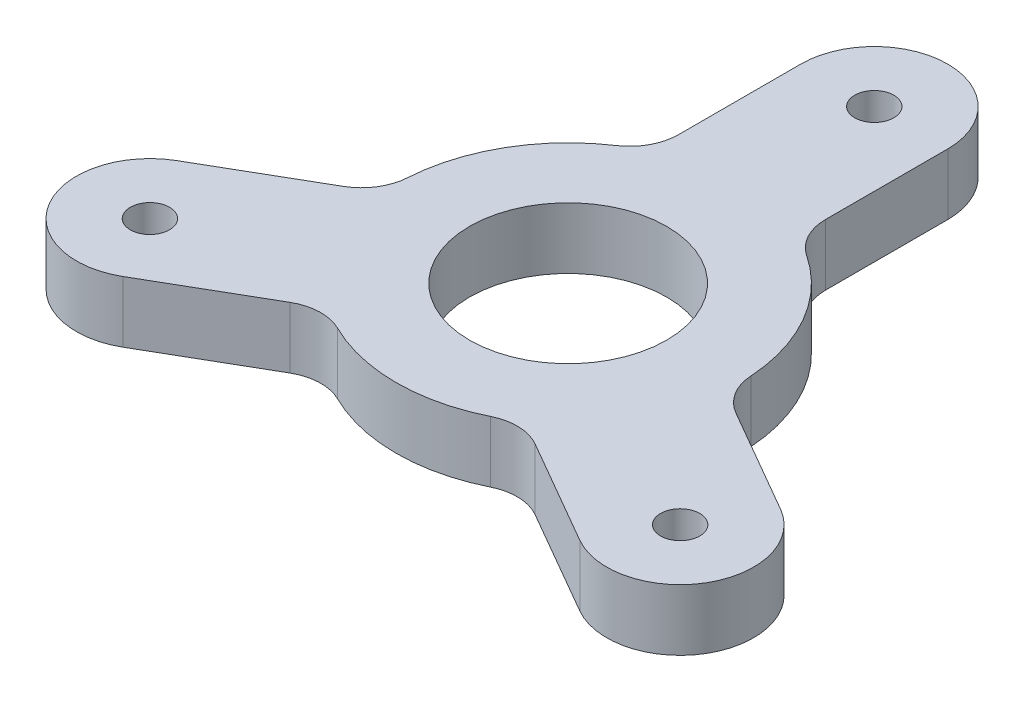
SolidWorks part; units mm, degrees
ref_plane "Front Plane" through (0, 0, 0) normal (0, 0, 1) x (1, 0, 0)
ref_plane "Top Plane" through (0, 0, 0) normal (0, 1, 0) x (1, 0, 0)
ref_plane "Right Plane" through (0, 0, 0) normal (1, 0, 0) x (0, 0, -1)
sketch "Sketch1" plane through (0, 0, 0) normal (0, 1, 0) x (1, 0, 0)
  line L0 (0, 0) -> (0, 9.0907) construction
  line L1 (0, 0) -> (7.1459, -4.1257) construction
  line L2 (0, 0) -> (-8.3205, -4.8039) construction
  line L3 (24.6506, -7.3038) -> (16.0135, -2.3172)
  line L4 (18.6506, -17.6962) -> (10.0135, -12.7095)
  line L5 (-18.6506, -17.6962) -> (-10.0135, -12.7095)
  line L6 (-24.6506, -7.3038) -> (-16.0135, -2.3172)
  line L7 (-6, 25) -> (-6, 15.0267)
  line L8 (6, 25) -> (6, 15.0267)
  circle A0 centre (0, 0) radius 8.05
  arc A1 (14.0216, 0.8927) -> (7.7839, 11.6967) centre (0, 0) ccw
  circle A2 centre (0, 25) radius 1.6
  circle A3 centre (0, 0) radius 25 construction
  circle A4 centre (21.6506, -12.5) radius 1.6
  circle A5 centre (-21.6506, -12.5) radius 1.6
  arc A6 (18.6506, -17.6962) -> (24.6506, -7.3038) centre (21.6506, -12.5) ccw
  arc A7 (-24.6506, -7.3038) -> (-18.6506, -17.6962) centre (-21.6506, -12.5) ccw
  arc A8 (6, 25) -> (-6, 25) centre (0, 25) ccw
  arc A9 (-7.7839, 11.6967) -> (-14.0216, 0.8927) centre (0, 0) ccw
  arc A10 (-6.2377, -12.5894) -> (6.2377, -12.5894) centre (0, 0) ccw
  arc A11 (-16.0135, -2.3172) -> (-14.0216, 0.8927) centre (-18.0135, 1.1469) ccw
  arc A12 (-10.0135, -12.7095) -> (-6.2377, -12.5894) centre (-8.0135, -16.1736) cw
  arc A13 (10.0135, -12.7095) -> (6.2377, -12.5894) centre (8.0135, -16.1736) ccw
  arc A14 (16.0135, -2.3172) -> (14.0216, 0.8927) centre (18.0135, 1.1469) cw
  arc A15 (6, 15.0267) -> (7.7839, 11.6967) centre (10, 15.0267) ccw
  arc A16 (-6, 15.0267) -> (-7.7839, 11.6967) centre (-10, 15.0267) cw
  point P36 (0, 0)
  dimension "D3" = 16.1
  dimension "D4" = 6
  dimension "D5" = 50
  dimension "D6" = 3.2
  dimension "D7" = 12
  dimension "D9" = 4
  dimension "D1" = 120
  dimension "D2" = 120
  dimension "D8" = 3
extrude "Boss-Extrude1" add sketch "Sketch1" along normal blind 5
